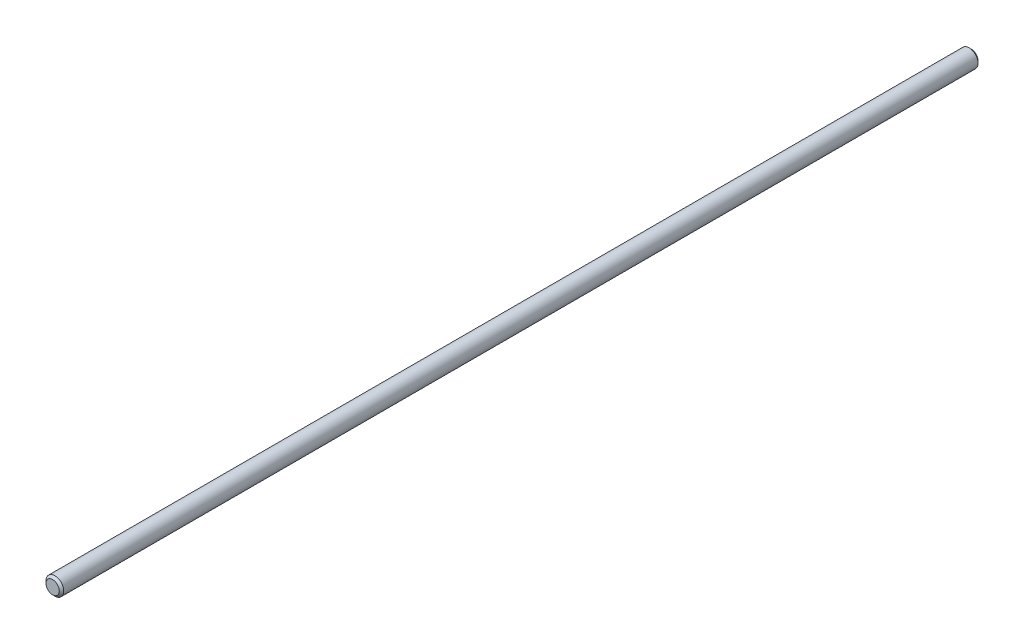
SolidWorks part; units mm, degrees
ref_plane "Piano frontale" through (0, 0, 0) normal (0, 0, 1) x (1, 0, 0)
ref_plane "Piano superiore" through (0, 0, 0) normal (0, 1, 0) x (1, 0, 0)
ref_plane "Piano destro" through (0, 0, 0) normal (1, 0, 0) x (0, 0, -1)
sketch "Schizzo1" plane through (0, 0, 0) normal (0, 0, 1) x (1, 0, 0)
  circle A0 centre (0, 0) radius 4
  dimension "D1" = 8
extrude "Estrusione-Estrusione1" add sketch "Schizzo1" along normal blind 415
chamfer "Smusso1" distance 1 angle 45 2 edges at (4, 0, 0) (4, 0, 415)
sketch "Schizzo2" plane through (0, 0, 0) normal (0, 1, 0) x (1, 0, 0)
  line L0 (4, -1) -> (4, -414) construction
